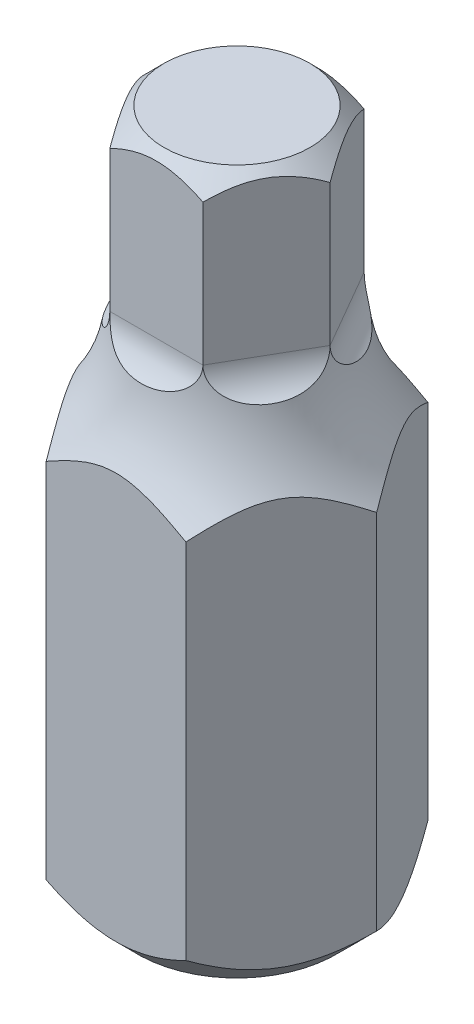
SolidWorks part; units mm, degrees
material "Stainless Steel (ferritic)"
ref_plane "Front Plane" through (0, 0, 0) normal (0, 0, 1) x (1, 0, 0)
ref_plane "Top Plane" through (0, 0, 0) normal (0, 1, 0) x (1, 0, 0)
ref_plane "Right Plane" through (0, 0, 0) normal (1, 0, 0) x (0, 0, -1)
sketch "Sketch1" plane through (0, 0, 0) normal (0, 1, 0) x (1, 0, 0)
  line L1 (2.3094, 0) -> (1.1547, 2)
  line L2 (1.1547, 2) -> (-1.1547, 2)
  line L3 (-1.1547, 2) -> (-2.3094, 0)
  line L4 (-2.3094, 0) -> (-1.1547, -2)
  line L5 (-1.1547, -2) -> (1.1547, -2)
  line L6 (1.1547, -2) -> (2.3094, 0)
  line L7 (3.4641, 0) -> (1.7321, 3)
  line L8 (1.7321, 3) -> (-1.7321, 3)
  line L9 (-1.7321, 3) -> (-3.4641, 0)
  line L10 (-3.4641, 0) -> (-1.7321, -3)
  line L11 (-1.7321, -3) -> (1.7321, -3)
  line L12 (1.7321, -3) -> (3.4641, 0)
  circle A0 centre (0, 0) radius 2 construction
  circle A1 centre (0, 0) radius 3 construction
  point P1 (0, 0)
  point P17 (0, 0)
  dimension "D1" = 4
  dimension "D2" = 6
extrude "Boss-Extrude1" add sketch "Sketch1" against normal blind 12 contours L11 L12 L7 L8 L9 L10
extrude "Boss-Extrude2" add sketch "Sketch1<3>" along normal blind 5 contours L5 L6 L1 L2 L3 L4
sketch "Sketch1<3>" plane through (0, 0, 0) normal (0, 1, 0) x (1, 0, 0) same geometry as "Sketch1"
fillet "Fillet1" radius 1 6 edges at (1.7321, 0, 1) (1.7321, 0, -1) (0, 0, -2) (-1.7321, 0, -1) (-1.7321, 0, 1) (0, 0, 2)
sketch "Sketch2" plane through (0, 0, 0) normal (0, 0, 1) x (1, 0, 0)
  line L0 (0, 5) -> (0, -12) construction
  line L1 (-1.1547, 5) -> (1.1547, 5) construction
  line L2 (-1.7321, -12) -> (1.7321, -12) construction
  line L3 (-3.4641, -12) -> (-3.4641, 5) construction
  line L6 (-3.4641, -12) -> (-3.4641, -11)
  line L8 (-1.8094, 5) -> (-2.3094, 5)
  line L9 (-2.3094, 5) -> (-1.1547, 5) construction
  line L10 (-2.3094, 5) -> (-2.3094, 4.5)
  line L11 (-2.3094, 4.5) -> (-1.8094, 5)
  line L12 (-3.4641, -11) -> (-2.4641, -12)
  line L13 (-2.3094, 5) -> (-2.3094, 1) construction
  line L14 (2.3094, 5) -> (2.3094, 1) construction
  line L15 (-2.4641, -12) -> (-3.4641, -12)
  line L16 (1.1547, 5) -> (2.3094, 5) construction
  line L17 (2.3094, 1) -> (6.8094, 1)
  line L18 (6.8094, 1) -> (6.8094, -3.5)
  arc A0 (6.8094, -3.5) -> (2.3094, 1) centre (6.8094, 1) cw
  point P21 (6.9584, -3.5)
  dimension "D6" = 4.5
  dimension "D1" = 45
  dimension "D2" = 0.5
  dimension "D3" = 45
  dimension "D4" = 1
  dimension "D5" = 4
revolve "Cut-Revolve1" cut sketch "Sketch2" angle 360 about L0
